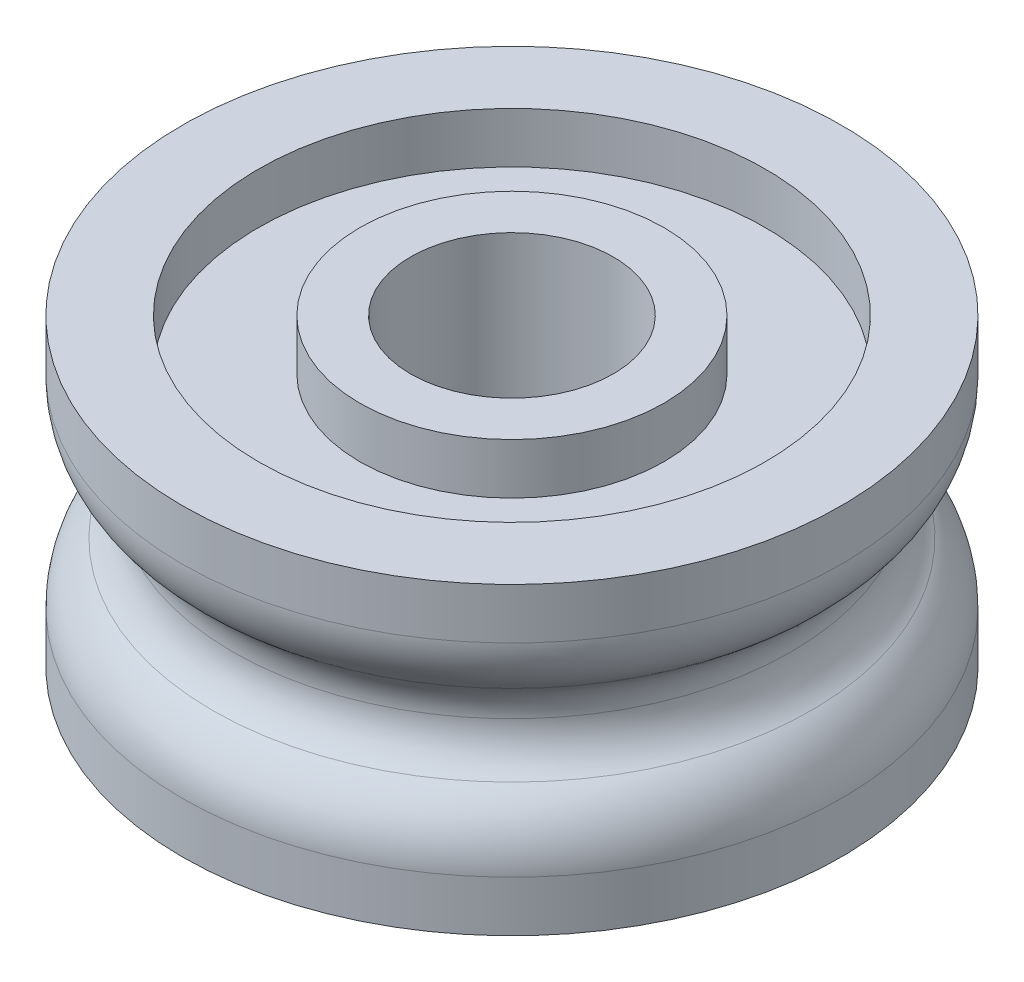
SolidWorks part; units mm, degrees
ref_plane "前视基准面" through (0, 0, 0) normal (0, 0, 1) x (1, 0, 0)
ref_plane "上视基准面" through (0, 0, 0) normal (0, 1, 0) x (1, 0, 0)
ref_plane "右视基准面" through (0, 0, 0) normal (1, 0, 0) x (0, 0, -1)
sketch "草图1" plane through (0, 0, 0) normal (0, 1, 0) x (1, 0, 0)
  circle A0 centre (0, 0) radius 2
  circle A1 centre (0, 0) radius 6.5
  dimension "D1" = 13
  dimension "D2" = 4
extrude "凸台-拉伸1" add sketch "草图1" along normal blind 6
sketch "草图2" plane through (0, 6, 0) normal (0, 1, 0) x (1, 0, 0)
  circle A0 centre (0, 0) radius 3
  circle A1 centre (0, 0) radius 5
  circle A2 centre (0, 0) radius 2 construction
  circle A3 centre (0, 0) radius 6.5 construction
  dimension "D1" = 1
  dimension "D2" = 1.5
extrude "切除-拉伸1" cut sketch "草图2" against normal blind 1
sketch "草图3" plane through (0, 0, 0) normal (0, -1, 0) x (-1, 0, 0)
  circle A0 centre (0, 0) radius 5
  circle A1 centre (0, 0) radius 3
  circle A2 centre (0, 0) radius 2 construction
  circle A3 centre (0, 0) radius 6.5 construction
  dimension "D1" = 1
  dimension "D2" = 1.5
extrude "切除-拉伸2" cut sketch "草图3" against normal blind 1
ref_plane "基准面1" through (6.5, 0, 0) normal (1, 0, 0) x (0, 0, -1)
ref_plane "基准面2" through (5.5, 0, 0) normal (1, 0, 0) x (0, 0, -1)
sketch "草图4" plane through (0, 0, 0) normal (0, 0, 1) x (1, 0, 0)
  line L0 (6.5, 0) -> (6.5, 6) construction
  line L1 (6.5, 4) -> (5.5, 4)
  line L2 (6.5, 4) -> (6.5, 2)
  line L3 (6.5, 2) -> (5.5, 2)
  line L4 (5.5, 4) -> (5.5, 2)
  line L5 (6, 4) -> (6, 6) construction
  line L6 (6.5, 6) -> (-6.5, 6) construction
  line L7 (6, 2) -> (6, 0) construction
  line L8 (-6.5, 0) -> (6.5, 0) construction
  line L9 (0, 0) -> (0, 6) construction
  line L10 (2, 6) -> (-2, 6) construction
  dimension "D1" = 1
  dimension "D2" = 2
revolve "切除-旋转1" cut sketch "草图4" angle 360 about L9
fillet "圆角1" radius 1 2 edges at (0, 2, -5.5) (0, 4, -5.5)
fillet "圆角2" radius 1.5 2 edges at (0, 2, -6.5) (0, 4, -6.5)
